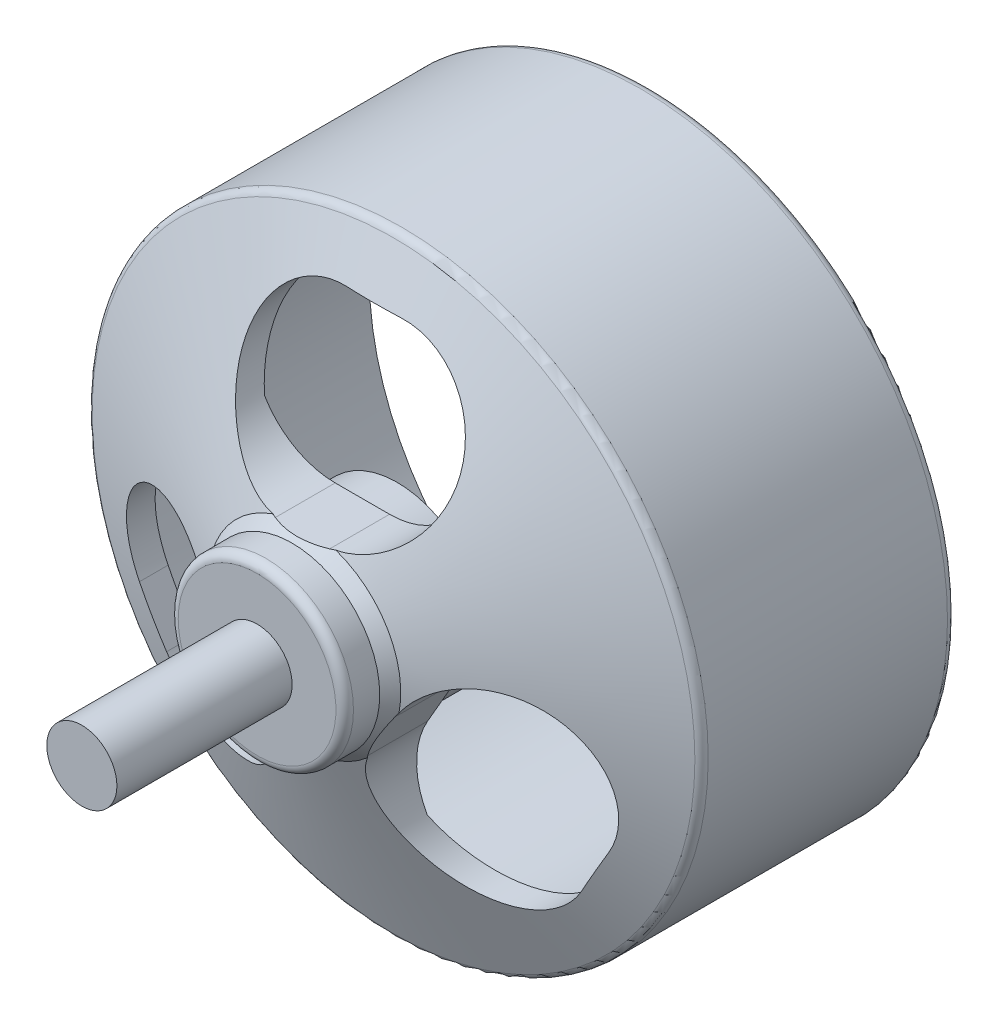
SolidWorks part; units mm, degrees
ref_plane "Спереди" through (0, 0, 0) normal (0, 0, 1) x (1, 0, 0)
ref_plane "Сверху" through (0, 0, 0) normal (0, 1, 0) x (1, 0, 0)
ref_plane "Справа" through (0, 0, 0) normal (1, 0, 0) x (0, 0, -1)
sketch "Эскиз1" plane through (0, 0, 0) normal (1, 0, 0) x (0, 0, -1)
  line L1 (-9, 0) -> (-9, 2)
  line L2 (-9, 2) -> (1, 2)
  line L3 (1, 2) -> (1, 5)
  line L4 (1, 5) -> (3, 5)
  line L5 (3, 5) -> (3.7, 5.5)
  line L6 (3.7, 5.5) -> (8.9165, 17.5)
  line L7 (8.9165, 17.5) -> (23.4, 17.5)
  line L8 (23.4, 17.5) -> (23.4, 16)
  line L9 (23.4, 16) -> (9.9, 16)
  line L10 (9.9, 16) -> (7.0092, 9.35)
  line L11 (7.0092, 9.35) -> (7.0092, 5)
  line L12 (7.0092, 5) -> (9, 5)
  line L13 (9, 5) -> (9, 0)
  line L15 (-9, 0) -> (9, 0)
  line L16 (9, 0) -> (20.1942, 0) construction
  dimension "D1" = 4
  dimension "D2" = 10
  dimension "D3" = 8
  dimension "D4" = 10
  dimension "D5" = 18.7
  dimension "D6" = 1.5
  dimension "D7" = 0.7
  dimension "D8" = 13.5
  dimension "D9" = 22.4
  dimension "D10" = 0.5
  dimension "D11" = 2
  dimension "D12" = 32
  dimension "D13" = 35
revolve "Повернуть1" add sketch "Эскиз1" angle 360 about L16
sketch "Эскиз2" plane through (0, 0, -1) normal (0, 0, 1) x (1, 0, 0)
  line L0 (1.55, 14.5641) -> (-1.55, 14.5641)
  line L1 (1.55, 5.1941) -> (-1.55, 5.1941)
  line L2 (1.55, 9.8791) -> (-1.55, 9.8791) construction
  line L3 (0, 9.8791) -> (0, 0) construction
  circle A0 centre (0, 0) radius 10 construction
  arc A1 (-1.55, 14.5641) -> (-1.55, 5.1941) centre (-1.55, 9.8791) ccw
  arc A2 (1.55, 5.1941) -> (1.55, 14.5641) centre (1.55, 9.8791) ccw
  dimension "D2" = 20
  dimension "D3" = 9.37
  dimension "D1" = 3.1
extrude "Вырез-Вытянуть1" cut sketch "Эскиз2" against normal blind 10
pattern_circular "Круговой массив1" count 3 over 360 about axis through (0, 0, -9) along (0, 0, 1) of "Вырез-Вытянуть1" reverse direction yes
fillet "Скругление1" radius 0.5 3 edges at (17.5, 0, -23.4) (17.5, 0, -8.9165) (5, 0, -1)
